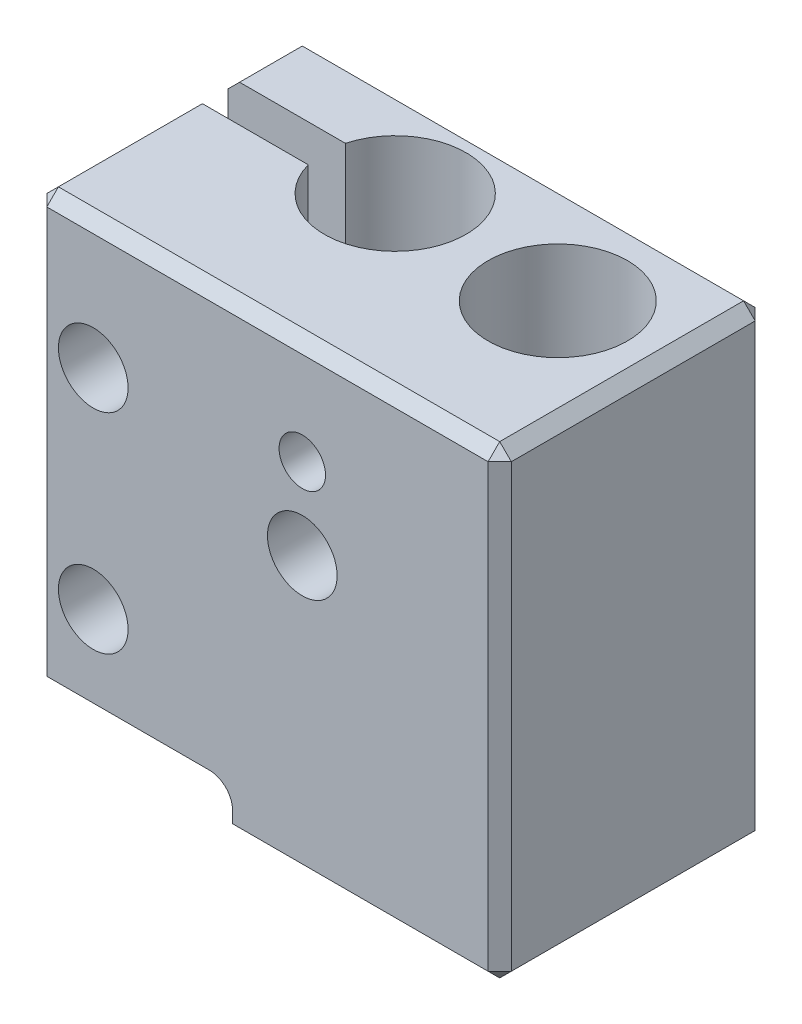
SolidWorks part; units mm, degrees
ref_plane "Front Plane" through (0, 0, 0) normal (0, 0, 1) x (1, 0, 0)
ref_plane "Top Plane" through (0, 0, 0) normal (0, 1, 0) x (1, 0, 0)
ref_plane "Right Plane" through (0, 0, 0) normal (1, 0, 0) x (0, 0, -1)
sketch "Sketch1" plane through (0, 0, 0) normal (0, 0, 1) x (1, 0, 0)
  line L0 (-10, 10) -> (10, 10)
  line L1 (-10, -10) -> (10, -10) construction
  line L2 (-10, -10) -> (-10, 10) construction
  line L3 (-10, 10) -> (10, 10) construction
  line L4 (10, -10) -> (10, 10) construction
  line L5 (-10, -10) -> (10, 10) construction
  line L6 (-10, 10) -> (10, -10) construction
  line L7 (10, 10) -> (10, -10)
  line L8 (-10, -8.5) -> (-10, 10)
  line L9 (-10, -8.5) -> (-2, -8.5)
  line L10 (-2, -8.5) -> (-2, -10)
  line L11 (-2, -10) -> (10, -10)
  point P0 (0, 0)
  dimension "D1" = 20
  dimension "D2" = 20
  dimension "D3" = 1.5
  dimension "D4" = 8
extrude "Boss-Extrude1" add sketch "Sketch1" along normal blind 11.5
sketch "Sketch2" plane through (0, 0, 11.5) normal (0, 0, 1) x (1, 0, 0)
  line L0 (-7.5, 10) -> (-7.5, -8.5) construction
  line L1 (10, 10) -> (-10, 10) construction
  line L2 (-10, -8.5) -> (-2, -8.5) construction
  line L3 (1.5, 10) -> (1.5, -10) construction
  line L4 (-2, -10) -> (10, -10) construction
  line L5 (-10, 10) -> (-10, -8.5) construction
  circle A0 centre (1.5, 2) radius 1.5
  circle A1 centre (1.5, 5.5) radius 1
  circle A2 centre (-7.5, 4.5) radius 1.5
  circle A3 centre (-7.5, -4.5) radius 1.5
  circle A4 centre (1.5, 5.5) radius 0.75
  dimension "D3" = 2
  dimension "D4" = 3
  dimension "D5" = 1.5
  dimension "D6" = 3
  dimension "D7" = 3
  dimension "D1" = 2.5
  dimension "D2" = 11.5
  dimension "D8" = 5.5
  dimension "D9" = 14.5
  dimension "D10" = 12
  dimension "D11" = 3.5
extrude "Cut-Extrude1" cut sketch "Sketch2" against normal through all contours A2 | A3 region at (-7.5, 4.5, 11.5) region at (-7.5, -4.5, 11.5)
extrude "Cut-Extrude2" cut sketch "Sketch2<3>" against normal blind 4.5 contours A4 region at (1.5, 5.5, 11.5)
sketch "Sketch2<3>" plane through (0, 0, 11.5) normal (0, 0, 1) x (1, 0, 0) same geometry as "Sketch2"
extrude "Cut-Extrude3" cut sketch "Sketch2<4>" against normal blind 2 contours A1
sketch "Sketch2<4>" plane through (0, 0, 11.5) normal (0, 0, 1) x (1, 0, 0) same geometry as "Sketch2"
extrude "Cut-Extrude4" cut sketch "Sketch2<5>" against normal blind 3.5 contours A0 region at (1.5, 2, 11.5)
sketch "Sketch2<5>" plane through (0, 0, 11.5) normal (0, 0, 1) x (1, 0, 0) same geometry as "Sketch2"
sketch "Sketch3" plane through (0, -10, 0) normal (0, -1, 0) x (1, 0, 0)
  line L0 (-10, 4) -> (10, 4) construction
  line L1 (-10, 11.5) -> (-10, 0) construction
  line L2 (10, 11.5) -> (10, 0) construction
  line L3 (-10, 4.5) -> (10, 4.5) construction
  line L4 (-10, 0) -> (-2, 0) construction
  line L5 (-2, 0) -> (10, 0) construction
  line L6 (-10, 4.8) -> (-4.9432, 4.8)
  line L7 (-10, 3.2) -> (-4.9432, 3.2)
  line L8 (-10, 4.8) -> (-10, 3.2)
  circle A0 centre (-2, 4) radius 3.05
  circle A1 centre (5.5, 4.5) radius 3
  line M4 (-2, 11.5) -> (-2, 0)
  dimension "D3" = 6
  dimension "D4" = 6.1
  dimension "D1" = 4
  dimension "D2" = 4.5
  dimension "D5" = 8
  dimension "D6" = 15.5
  dimension "D7" = 3.2
  dimension "D8" = 4.8
extrude "Cut-Extrude5" cut sketch "Sketch3" against normal through all contours A0 L6 L8 L7 | A0 M4 | A0 M4 region at (-7.5072, -10, 4) region at (-3.2945, -10, 4) region at (-0.7055, -10, 4)
extrude "Cut-Extrude6" cut sketch "Sketch3<4>" against normal through all contours A1 region at (5.5, -10, 4.5)
sketch "Sketch3<4>" plane through (0, -10, 0) normal (0, -1, 0) x (1, 0, 0) same geometry as "Sketch3"
fillet "Fillet1" radius 0.5 4 edges at (-2, -8.5, 0.475) (-2, -10, 9.275) (-2, -8.5, 9.275) (-2, -10, 0.475)
chamfer "Chamfer1" distance 0.5 angle 45 22 edges at (4.25, -10, 0) (-6.25, -8.5, 11.5) (-1.8536, -9.8536, 0) (-2.1464, -8.6464, 11.5) (-2, -9.25, 0) (-2, -9.25, 11.5) (-2.1464, -8.6464, 0) (-1.8536, -9.8536, 11.5) (10, 10, 5.75) (-6.25, -8.5, 0) (-10, -8.5, 1.6) (-10, 0.75, 0) (-10, 10, 1.6) (0, 10, 0) (10, 0, 0) (10, -10, 5.75) (-10, -8.5, 8.15) (-10, 10, 8.15) (-10, 0.75, 11.5) (0, 10, 11.5) (10, 0, 11.5) (4.25, -10, 11.5)
